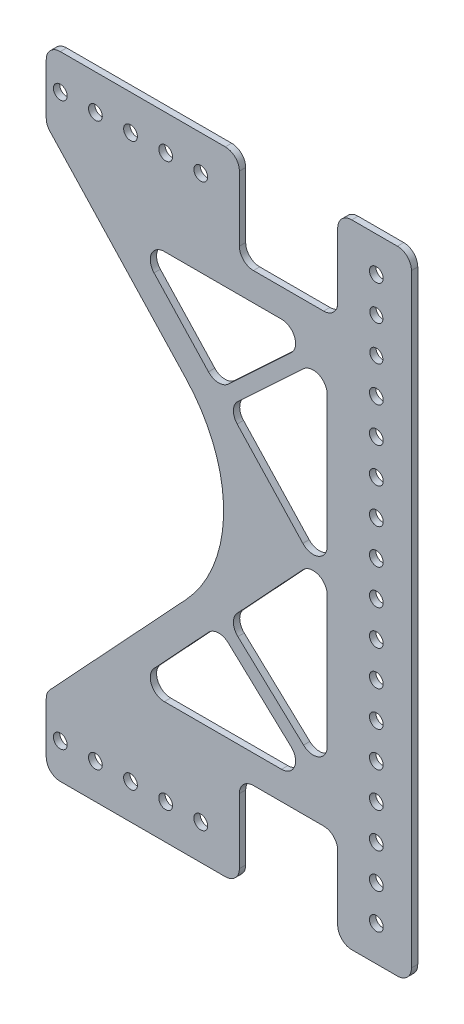
SolidWorks part; units mm, degrees
ref_plane "Front Plane" through (0, 0, 0) normal (0, 0, 1) x (1, 0, 0)
ref_plane "Top Plane" through (0, 0, 0) normal (0, 1, 0) x (1, 0, 0)
ref_plane "Right Plane" through (0, 0, 0) normal (1, 0, 0) x (0, 0, -1)
sketch "Sketch1" plane through (0, 0, 0) normal (0, 0, 1) x (1, 0, 0)
  line L11 (65.4076, 898.4977) -> (48.8976, 898.4977)
  line L12 (43.8176, 893.4177) -> (43.8176, 869.9227)
  line L13 (38.7376, 864.8427) -> (13.3376, 864.8427)
  line L14 (8.2576, 869.9227) -> (8.2576, 893.4177)
  line L15 (3.1776, 898.4977) -> (-56.5124, 898.4977)
  line L16 (-60.2304, 871.6349) -> (-11.0513, 818.8143)
  line L17 (70.4876, 893.4177) -> (70.4876, 784.1977)
  line L18 (-61.5924, 875.0965) -> (-61.5924, 893.4177)
  line L20 (-22.6122, 846.1411) -> (-2.9253, 824.9965)
  line L21 (40.0076, 791.7957) -> (40.0076, 839.4169)
  line L22 (23.5028, 854.6827) -> (-18.8942, 854.6827)
  line L23 (70.4876, 674.9777) -> (70.4876, 784.1977)
  line L24 (65.4076, 669.8977) -> (48.8976, 669.8977)
  line L25 (43.8176, 674.9777) -> (43.8176, 698.4727)
  line L26 (38.7376, 703.5527) -> (13.3376, 703.5527)
  line L27 (8.2576, 698.4727) -> (8.2576, 674.9777)
  line L28 (-60.2304, 696.7606) -> (-11.0513, 749.5812)
  line L29 (3.1776, 669.8977) -> (-56.5124, 669.8977)
  line L30 (-61.5924, 693.2989) -> (-61.5924, 674.9777)
  line L31 (26.9645, 845.8848) -> (4.2543, 824.7402)
  line L32 (7.4596, 754.5529) -> (31.2096, 780.0614)
  line L33 (31.4659, 843.1349) -> (7.716, 821.0222)
  line L34 (7.4596, 813.8426) -> (31.2096, 788.3341)
  line L35 (40.0076, 776.5997) -> (40.0076, 728.9785)
  line L36 (31.4659, 725.2606) -> (7.716, 747.3732)
  line L37 (26.9645, 722.5107) -> (4.2543, 743.6552)
  line L38 (-22.6122, 722.2544) -> (-2.9253, 743.3989)
  line L39 (23.5028, 713.7127) -> (-18.8942, 713.7127)
  arc A1 (65.4076, 898.4977) -> (70.4876, 893.4177) centre (65.4076, 893.4177) cw
  arc A2 (48.8976, 898.4977) -> (43.8176, 893.4177) centre (48.8976, 893.4177) ccw
  arc A3 (43.8176, 869.9227) -> (38.7376, 864.8427) centre (38.7376, 869.9227) cw
  arc A4 (13.3376, 864.8427) -> (8.2576, 869.9227) centre (13.3376, 869.9227) cw
  arc A5 (8.2576, 893.4177) -> (3.1776, 898.4977) centre (3.1776, 893.4177) ccw
  arc A6 (-56.5124, 898.4977) -> (-61.5924, 893.4177) centre (-56.5124, 893.4177) ccw
  circle A7 centre (-31.1124, 885.7977) radius 2.4892
  circle A8 centre (-18.4124, 885.7977) radius 2.4892
  circle A9 centre (-5.7124, 885.7977) radius 2.4892
  circle A11 centre (57.7876, 860.3977) radius 2.3719
  circle A12 centre (57.7876, 847.6977) radius 2.4892
  circle A13 centre (57.7876, 834.9977) radius 2.4892
  circle A14 centre (57.7876, 822.2977) radius 2.4892
  circle A15 centre (57.7876, 809.5977) radius 2.4892
  arc A16 (-60.2304, 871.6349) -> (-61.5924, 875.0965) centre (-56.5124, 875.0965) cw
  arc A17 (31.2096, 788.3341) -> (40.0076, 791.7957) centre (34.9276, 791.7957) ccw
  arc A18 (-22.6122, 846.1411) -> (-18.8942, 854.6827) centre (-18.8942, 849.6027) cw
  arc A19 (65.4076, 669.8977) -> (70.4876, 674.9777) centre (65.4076, 674.9777) ccw
  arc A20 (48.8976, 669.8977) -> (43.8176, 674.9777) centre (48.8976, 674.9777) cw
  arc A21 (43.8176, 698.4727) -> (38.7376, 703.5527) centre (38.7376, 698.4727) ccw
  arc A22 (13.3376, 703.5527) -> (8.2576, 698.4727) centre (13.3376, 698.4727) ccw
  arc A23 (8.2576, 674.9777) -> (3.1776, 669.8977) centre (3.1776, 674.9777) cw
  circle A24 centre (-5.7124, 682.5977) radius 2.4892
  circle A25 centre (-18.4124, 682.5977) radius 2.4892
  circle A26 centre (-31.1124, 682.5977) radius 2.4892
  arc A27 (-60.2304, 696.7606) -> (-61.5924, 693.2989) centre (-56.5124, 693.2989) ccw
  arc A28 (-56.5124, 669.8977) -> (-61.5924, 674.9777) centre (-56.5124, 674.9777) cw
  circle A29 centre (57.7876, 733.3977) radius 2.4892
  circle A30 centre (57.7876, 720.6977) radius 2.4892
  circle A31 centre (57.7876, 707.9977) radius 2.4892
  circle A32 centre (57.7876, 682.5977) radius 2.4892
  circle A33 centre (57.7876, 885.7977) radius 2.4892
  arc A34 (-11.0513, 818.8143) -> (-11.0513, 749.5812) centre (-48.231, 784.1977) cw
  circle A35 centre (57.7876, 771.4977) radius 2.4892
  circle A36 centre (57.7876, 758.7977) radius 2.4892
  circle A37 centre (57.7876, 746.0977) radius 2.4892
  circle A38 centre (-56.5124, 885.7977) radius 2.4892
  circle A39 centre (-43.8124, 885.7977) radius 2.4892
  circle A40 centre (-43.8124, 682.5977) radius 2.4892
  circle A41 centre (-56.5124, 682.5977) radius 2.4892
  arc A42 (7.716, 821.0222) -> (7.4596, 813.8426) centre (11.1776, 817.3043) ccw
  arc A43 (31.4659, 843.1349) -> (40.0076, 839.4169) centre (34.9276, 839.4169) cw
  arc A44 (26.9645, 845.8848) -> (23.5028, 854.6827) centre (23.5028, 849.6027) ccw
  arc A45 (4.2543, 824.7402) -> (-2.9253, 824.9965) centre (0.7927, 828.4582) cw
  arc A46 (31.2096, 780.0614) -> (40.0076, 776.5997) centre (34.9276, 776.5997) cw
  arc A47 (7.716, 747.3732) -> (7.4596, 754.5529) centre (11.1776, 751.0912) cw
  arc A48 (31.4659, 725.2606) -> (40.0076, 728.9785) centre (34.9276, 728.9785) ccw
  arc A49 (26.9645, 722.5107) -> (23.5028, 713.7127) centre (23.5028, 718.7927) cw
  arc A50 (4.2543, 743.6552) -> (-2.9253, 743.3989) centre (0.7927, 739.9373) ccw
  arc A51 (-22.6122, 722.2544) -> (-18.8942, 713.7127) centre (-18.8942, 718.7927) ccw
  circle A52 centre (57.7876, 796.8977) radius 2.4892
  circle A53 centre (57.7876, 784.1977) radius 2.4892
  circle A54 centre (57.7876, 873.0977) radius 2.3719
  circle A55 centre (57.7876, 695.2977) radius 2.4892
  point P14 (70.4876, 784.1977)
  point P17 (45.0876, 784.1977)
  dimension "D1" = 10.16
  dimension "D3" = 5.08
  dimension "D4" = 50.8
  dimension "D5" = 5.08
  dimension "D6" = 5.08
  dimension "D8" = 5.08
  dimension "D11" = 12.7
  dimension "D12" = 12.7
  dimension "D2" = 10.16
  dimension "D7" = 5.08
  dimension "D9" = 3
  dimension "D10" = 2
extrude "Boss-Extrude2" add sketch "Sketch1" along normal blind 2.286 contours L16 A34 L28 A27 L30 A28 L29 A23 L27 A22 L26 A21 L25 A20 L24 A19 L23 L17 A1 L11 A2 L12 A3 L13 A4 L14 A5 L15 A6 L18 A16 A55 A54 A53 A52 A51 L38 A50 L37 A49 L39 A48 L36 A47 L32 region at (15.2139, 784.2164, 0)
